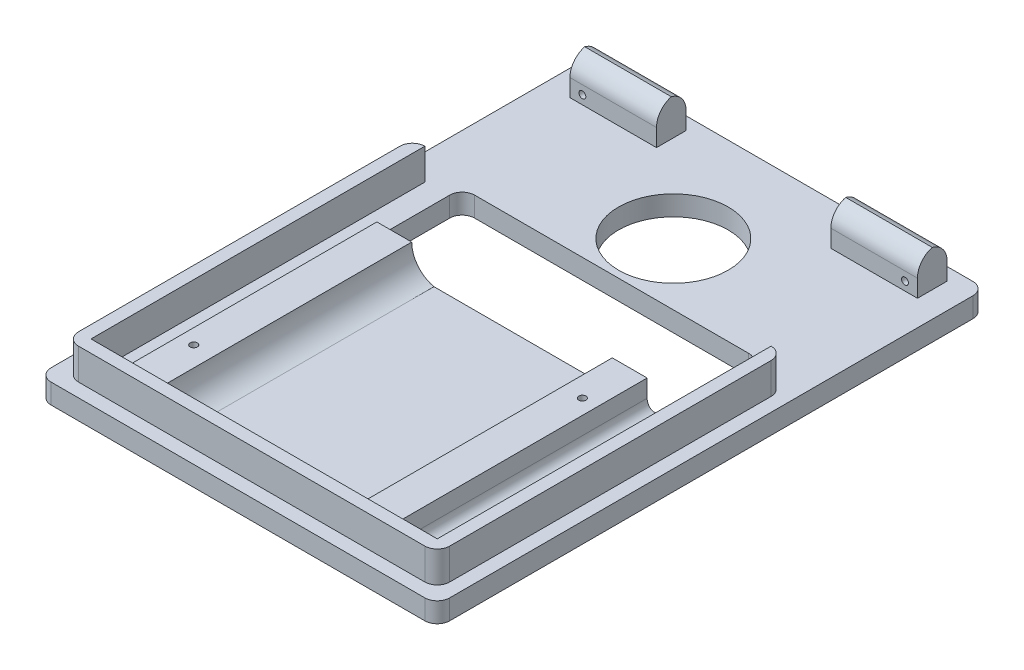
SolidWorks part; units mm, degrees
ref_plane "Front Plane" through (0, 0, 0) normal (0, 0, 1) x (1, 0, 0)
ref_plane "Top Plane" through (0, 0, 0) normal (0, 1, 0) x (1, 0, 0)
ref_plane "Right Plane" through (0, 0, 0) normal (1, 0, 0) x (0, 0, -1)
sketch "Sketch3" plane through (0, 0, 0) normal (0, 1, 0) x (1, 0, 0)
  line L0 (-75, 110) -> (75, 110)
  line L1 (-75, -105) -> (75, -105)
  line L2 (-75, -105) -> (-75, 105)
  line L4 (75, -105) -> (75, 105)
  line L5 (-75, -105) -> (75, 105) construction
  line L6 (-75, 105) -> (75, -105) construction
  line L7 (80, -105) -> (80, 105)
  line L8 (-75, -110) -> (75, -110)
  line L9 (-80, -105) -> (-80, 105)
  line L10 (-80, -110) -> (80, -110) construction
  line L11 (-80, -110) -> (-80, 110) construction
  line L12 (80, -110) -> (80, 110) construction
  line L13 (-80, 110) -> (80, 110) construction
  line L15 (-75, 105) -> (75, 105)
  line L19 (-75, 105) -> (75, 105) construction
  line L20 (-69.75, 104.9) -> (69.75, 104.9)
  line L21 (-69.75, 104.9) -> (-69.75, 93)
  line L22 (-69.75, 93) -> (69.75, 93)
  line L23 (69.75, 104.9) -> (69.75, 93)
  arc A0 (-75, -110) -> (-80, -105) centre (-75, -105) cw
  arc A1 (80, -105) -> (75, -110) centre (75, -105) cw
  arc A2 (75, 110) -> (80, 105) centre (75, 105) cw
  arc A3 (-75, 110) -> (-80, 105) centre (-75, 105) ccw
  point P0 (0, 0)
  point P5 (0, 93)
  dimension "D4" = 5
  dimension "D1" = 75
  dimension "D2" = 210
  dimension "D5" = 11.9
  dimension "D6" = 139.5
  dimension "D7" = 0.1
  dimension "D3" = 5
extrude "Boss-Extrude1" add sketch "Sketch3" along normal blind 8 contours L1 L4 L2 | L0 A3 L9 A0 L8 A1 L7 A2 L4 L1 L2 | L2 L4 | L23 L15 L21 L22 region at (0, 0, -107.2797) region at (0, 0, 5.5048) region at (0, 0, -98.95)
extrude "Boss-Extrude2" add sketch "Sketch3<7>" along normal blind 15 from surface contours L23 L15 L21 L22 region at (0, 0, -98.95) starting at face at (0, 8, 0)
sketch "Sketch3<7>" plane through (0, 0, 0) normal (0, 1, 0) x (1, 0, 0) same geometry as "Sketch3"
fillet "Fillet1" radius 8 2 edges at (0, 23, -93) (0, 23, -104.9)
sketch "Sketch4" plane through (0, 0, 0) normal (0, -1, 0) x (1, 0, 0)
  line L1 (-55, 0) -> (55, 0)
  line L2 (-60, -5) -> (-60, -35)
  line L3 (-55, -40) -> (55, -40)
  line L4 (60, -5) -> (60, -35)
  line L5 (-75, 110) -> (75, 110) construction
  line L6 (80, 105) -> (80, -105) construction
  line L7 (-75, -110) -> (75, -110) construction
  arc A0 (-55, 0) -> (-60, -5) centre (-55, -5) ccw
  arc A1 (-60, -35) -> (-55, -40) centre (-55, -35) ccw
  arc A2 (55, -40) -> (60, -35) centre (55, -35) ccw
  arc A3 (55, 0) -> (60, -5) centre (55, -5) cw
  point P4 (0, -40)
  dimension "D4" = 5
  dimension "D1" = 70
  dimension "D2" = 110
  dimension "D3" = 20
extrude "Cut-Extrude1" cut sketch "Sketch4" against normal up to next
sketch "Sketch5" plane through (0, 8, 0) normal (0, 1, 0) x (1, 0, 0)
  line L0 (75, -105) -> (75, 105) construction
  line L1 (-75, -105) -> (75, -105) construction
  line L2 (-75, -105) -> (-75, 105) construction
  line L3 (-75, 105) -> (75, 105) construction
  line L4 (75, 110) -> (-75, 110)
  line L5 (80, -105) -> (80, 105)
  line L6 (-75, -110) -> (75, -110)
  line L7 (-80, 105) -> (-80, -105)
  line L8 (75, 110) -> (-75, 110)
  line L9 (80, -105) -> (80, 105)
  line L10 (-75, -110) -> (75, -110)
  line L11 (-80, 105) -> (-80, -105)
  line L12 (69.75, 104.9) -> (-69.75, 104.9)
  line L13 (-69.75, 104.9) -> (-69.75, 93)
  line L14 (-69.75, 93) -> (69.75, 93)
  line L15 (69.75, 93) -> (69.75, 104.9)
  line L16 (69.75, 104.9) -> (-69.75, 104.9)
  line L17 (-69.75, 104.9) -> (-69.75, 93)
  line L18 (-69.75, 93) -> (69.75, 93)
  line L19 (69.75, 93) -> (69.75, 104.9)
  line L20 (75, -105) -> (75, 105)
  line L21 (-75, -105) -> (75, -105)
  line L22 (-75, -105) -> (-75, 105)
  line L23 (-75, 105) -> (75, 105)
  line L24 (-75, 35) -> (75, 35)
  line L25 (-69.5, 34.5) -> (-69.5, -99.5)
  line L26 (-69.5, -104.5) -> (69.5, -104.5)
  line L27 (-74.5, -99.5) -> (-74.5, 29.5)
  line L28 (-69.5, 34.5) -> (69.5, 34.5)
  line L29 (74.5, -99.5) -> (74.5, 29.5)
  line L30 (-69.5, -99.5) -> (69.5, -99.5)
  line L31 (69.5, -99.5) -> (69.5, 34.5)
  arc A0 (-74.5, 29.5) -> (-69.5, 34.5) centre (-69.5, 29.5) cw
  arc A1 (69.5, 34.5) -> (74.5, 29.5) centre (69.5, 29.5) cw
  arc A2 (69.5, -104.5) -> (74.5, -99.5) centre (69.5, -99.5) ccw
  arc A3 (-69.5, -104.5) -> (-74.5, -99.5) centre (-69.5, -99.5) cw
  arc A4 (80, 105) -> (75, 110) centre (75, 105) ccw
  arc A5 (75, -110) -> (80, -105) centre (75, -105) ccw
  arc A6 (-80, -105) -> (-75, -110) centre (-75, -105) ccw
  arc A7 (-75, 110) -> (-80, 105) centre (-75, 105) ccw
  arc A8 (80, 105) -> (75, 110) centre (75, 105) ccw
  arc A9 (75, -110) -> (80, -105) centre (75, -105) ccw
  arc A10 (-80, -105) -> (-75, -110) centre (-75, -105) ccw
  arc A11 (-75, 110) -> (-80, 105) centre (-75, 105) ccw
  point P26 (0, -104.5)
  point P42 (0, -99.5)
  dimension "D7" = 5
  dimension "D3" = 75
  dimension "D4" = 0.5
  dimension "D5" = 0.5
  dimension "D6" = 0.5
  dimension "D8" = 5
  dimension "D9" = 5
  dimension "D1" = 0
  dimension "D2" = 0
extrude "Boss-Extrude3" add sketch "Sketch5" along normal blind 12.5 contours A3 L26 A2 L29 A1 L31 L30 L25 A0 L27 region at (-71.5377, 8, 32.5)
sketch "Sketch6" plane through (0, 0, -104.9) normal (0, 0, -1) x (-1, 0, 0)
  line L0 (-69.75, 15) -> (-69.75, 8) construction
  line L1 (0, 0) -> (0, 22.7329) construction
  line L2 (-69.75, 22.7329) -> (69.75, 22.7329) construction
  circle A0 centre (-64.75, 11.5) radius 1.375
  circle A1 centre (64.75, 11.5) radius 1.375
  point P5 (-69.75, 11.5)
  dimension "D1" = 2.75
  dimension "D2" = 5
extrude "Cut-Extrude2" cut sketch "Sketch6" against normal up to next
sketch "Sketch8" plane through (0, 0, 99.5) normal (0, 0, -1) x (-1, 0, 0)
  line L0 (-28.95, 19.05) -> (28.95, 19.05) construction
  line L1 (-28.95, 30.1) -> (28.95, 30.1)
  line L2 (-28.95, 8) -> (28.95, 8)
  line L3 (69.5, 8) -> (-69.5, 8) construction
  line L4 (0, 19.05) -> (0, 0) construction
  line L5 (-28.95, 30.35) -> (28.95, 30.35)
  line L6 (-28.95, 7.75) -> (28.95, 7.75)
  line L7 (-28.95, 33.35) -> (28.95, 33.35)
  line L8 (-28.95, 4.75) -> (28.95, 4.75)
  line L9 (-38.0268, 8) -> (38.0268, 8)
  line L10 (-43.25, 19.05) -> (43.25, 19.05)
  line L11 (-28.95, 4.75) -> (-54.25, 4.75)
  line L12 (-54.25, 4.75) -> (-54.25, 19.05)
  line L13 (-54.25, 19.05) -> (-43.25, 19.05)
  line L14 (54.25, 19.05) -> (43.25, 19.05)
  line L15 (28.95, 4.75) -> (54.25, 4.75)
  line L16 (54.25, 4.75) -> (54.25, 19.05)
  line L18 (-54.25, 19.05) -> (-54.0716, 19.05)
  line L19 (-54.0716, 19.05) -> (-54.0716, 21.05)
  line L20 (-54.0716, 21.05) -> (-40.0716, 21.05)
  line L21 (54.0716, 21.05) -> (40.0716, 21.05)
  line L22 (54.0716, 19.05) -> (54.0716, 21.05)
  line L23 (54.25, 19.05) -> (54.0716, 19.05)
  arc A0 (-28.95, 30.1) -> (-28.95, 8) centre (-28.95, 19.05) ccw
  arc A1 (28.95, 8) -> (28.95, 30.1) centre (28.95, 19.05) ccw
  arc A2 (28.95, 7.75) -> (28.95, 30.35) centre (28.95, 19.05) ccw
  arc A3 (-28.95, 30.35) -> (-28.95, 7.75) centre (-28.95, 19.05) ccw
  arc A4 (28.95, 4.75) -> (28.95, 33.35) centre (28.95, 19.05) ccw
  arc A5 (-28.95, 33.35) -> (-28.95, 4.75) centre (-28.95, 19.05) ccw
  point P2 (0, 19.05)
  point P29 (0, 19.05)
  line M6 (-69.5, 8) -> (69.5, 8)
  line M8 (69.5, 20.5) -> (-69.5, 20.5)
  dimension "D2" = 80
  dimension "D5" = 14
  dimension "D1" = 22.1
  dimension "D6" = 14
  dimension "D7" = 2
  dimension "D3" = 0.25
  dimension "D4" = 3
extrude "Boss-Extrude4" add sketch "Sketch8" along normal up to surface (99.5 mm away) contours L9 A4 A2 M8 | A5 A3 M8 M6 | A4 L16 L14 M6 | A5 L13 L12 M6 region at (39.4137, 12.9121, 99.5) region at (-39.4137, 12.9121, 99.5) region at (47.8657, 13.1621, 99.5) region at (-47.8657, 13.1621, 99.5) up to face at (0, 4, 0)
sketch "Sketch9" plane through (0, 8, 0) normal (0, 1, 0) x (1, 0, 0)
  line L0 (69.75, 98.95) -> (-69.75, 98.95) construction
  line L1 (-35, 104.9) -> (35, 104.9)
  line L2 (-35, 104.9) -> (-35, 93)
  line L3 (-35, 93) -> (35, 93)
  line L4 (35, 104.9) -> (35, 93)
  line L5 (-35, 104.9) -> (35, 93) construction
  line L6 (-35, 93) -> (35, 104.9) construction
  line L7 (69.75, 93) -> (-69.75, 93) construction
  point P0 (0, 98.95)
  dimension "D1" = 70
extrude "Cut-Extrude3" cut sketch "Sketch9" along normal up to next
sketch "Sketch11" plane through (0, 0, 0) normal (0, -1, 0) x (1, 0, 0)
  circle A0 centre (0, -64.78) radius 22
  dimension "D1" = 44
extrude "Cut-Extrude5" cut sketch "Sketch11" against normal up to next
fillet "Fillet2" radius 4 2 edges at (54.25, 8, 49.75) (-54.25, 8, 49.75)
sketch "Sketch12" plane through (0, 19.05, 0) normal (0, 1, 0) x (1, 0, 0)
  line L0 (40.25, 0) -> (54.25, 0) construction
  line L1 (-69.5, -99.5) -> (69.5, -99.5) construction
  line L4 (40.25, 0) -> (40.25, -99.5) construction
  line L5 (-40.25, 0) -> (-40.25, -99.5) construction
  circle A0 centre (48.25, -20) radius 1.45
  circle A1 centre (-48.25, -79.5) radius 1.45
  dimension "D1" = 2.9
  dimension "D4" = 8
  dimension "D5" = 8
  dimension "D2" = 20
  dimension "D3" = 20
extrude "Cut-Extrude6" cut sketch "Sketch12" against normal up to next
sketch "Sketch13" plane through (0, 0, 0) normal (0, -1, 0) x (1, 0, 0)
  circle A0 centre (-48.25, 79.5) radius 2.5
  circle A1 centre (48.25, 20) radius 2.5
  dimension "D1" = 5
extrude "Cut-Extrude7" cut sketch "Sketch13" against normal blind 4
